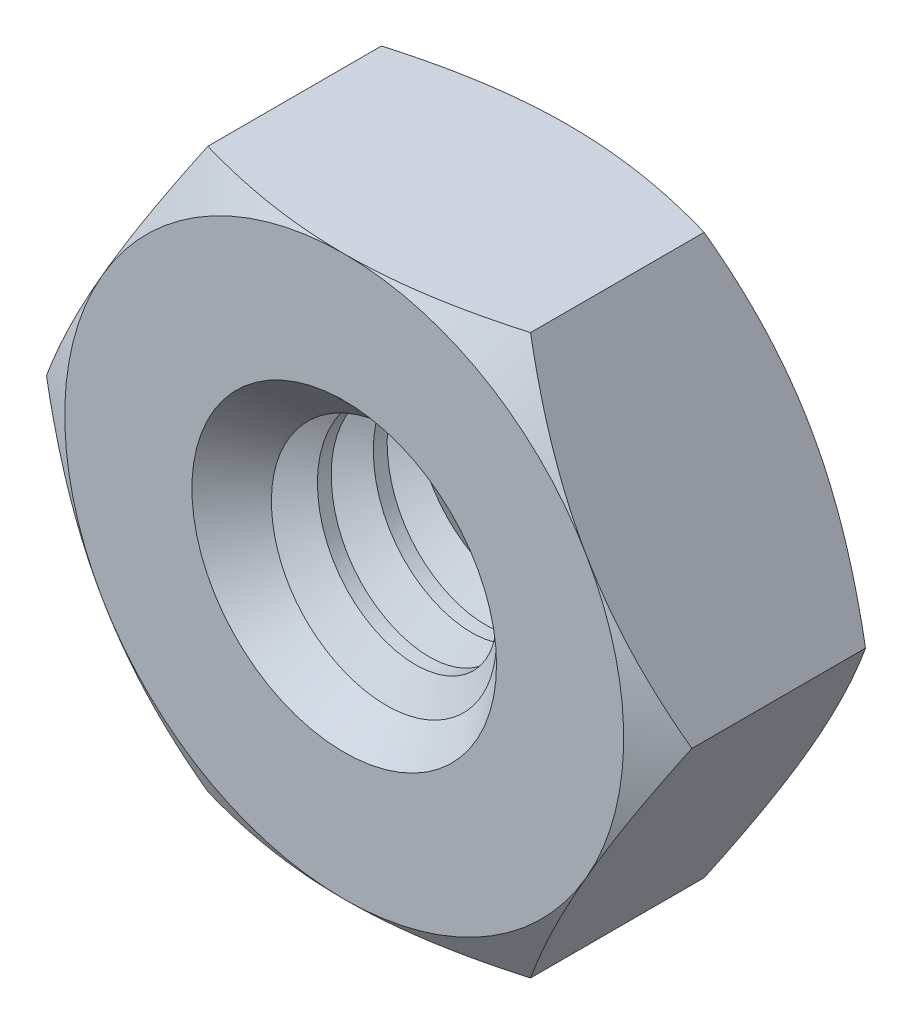
SolidWorks part; units mm, degrees
ref_plane "Front" through (0, 0, 0) normal (0, 0, 1) x (1, 0, 0)
ref_plane "Top" through (0, 0, 0) normal (0, 1, 0) x (1, 0, 0)
ref_plane "Right" through (0, 0, 0) normal (1, 0, 0) x (0, 0, -1)
sketch "Çizim1" plane through (0, 0, 0) normal (0, 0, 1) x (1, 0, 0)
  line L1 (2.3094, 0) -> (1.1547, 2)
  line L2 (1.1547, 2) -> (-1.1547, 2)
  line L3 (-1.1547, 2) -> (-2.3094, 0)
  line L4 (-2.3094, 0) -> (-1.1547, -2)
  line L5 (-1.1547, -2) -> (1.1547, -2)
  line L6 (1.1547, -2) -> (2.3094, 0)
  circle A0 centre (0, 0) radius 2 construction
  point P1 (0, 0)
  dimension "D1" = 4
extrude "Yükseklik-Ekstrüzyon1" add sketch "Çizim1" along normal blind 1.6
sketch "Çizim2" plane through (0, 0, 1.6) normal (0, 0, 1) x (1, 0, 0)
  circle A0 centre (0, 0) radius 2
extrude "Kes-Ekstrüzyon1" cut sketch "Çizim2" against normal blind 1.6 draft 60 flip side to cut
sketch "Çizim3" plane through (0, 0, 0) normal (0, 0, -1) x (-1, 0, 0)
  circle A0 centre (0, 0) radius 2
extrude "Kes-Ekstrüzyon2" cut sketch "Çizim3" against normal blind 1.6 draft 60 flip side to cut
sketch "Çizim4" plane through (0, 0, 0) normal (0, 0, -1) x (-1, 0, 0)
  circle A0 centre (0, 0) radius 0.74
  dimension "D1" = 1.48
extrude "Kes-Ekstrüzyon3" cut sketch "Çizim4" against normal blind 1.6
chamfer "Pah1" distance 0.35 angle 45 2 edges at (-0.74, 0, 1.6) (-0.74, 0, 0)
sketch "Çizim5" plane through (0, 0, 1.6) normal (0, 0, 1) x (1, 0, 0)
  circle A0 centre (0, 0) radius 0.74
curve "Helis/Spiral1" pitch 0.4 height 2 radius 0.74 centre (0, 0, 1.6) axis (0, 0, -1) start towards (-1, 0, 0)
ref_plane "Düzlem1" through (-0.74, 0, -0.4) normal (0, 0.9963, -0.0857) x (1, 0, 0)
sketch "Çizim6" plane through (-0.74, 0, -0.4) normal (0, 0.9963, -0.0857) x (1, 0, 0)
  line L0 (0.0779, 0.1951) -> (0.0779, -0.1951)
  line L1 (-0.26, 0) -> (0.0779, -0.1951)
  line L3 (0.0779, 0.1951) -> (-0.26, 0)
  line L4 (0.13, 0) -> (0.13, 0.2252) [skipped]
  arc A0 (0.0779, 0.1041) -> (0.0779, -0.1041) centre (0, 0) ccw construction
  dimension "D1" = 0.26
sweep "Kes-Süpür1" cut profiles "Çizim6" path "Helis/Spiral1" align with end faces yes
